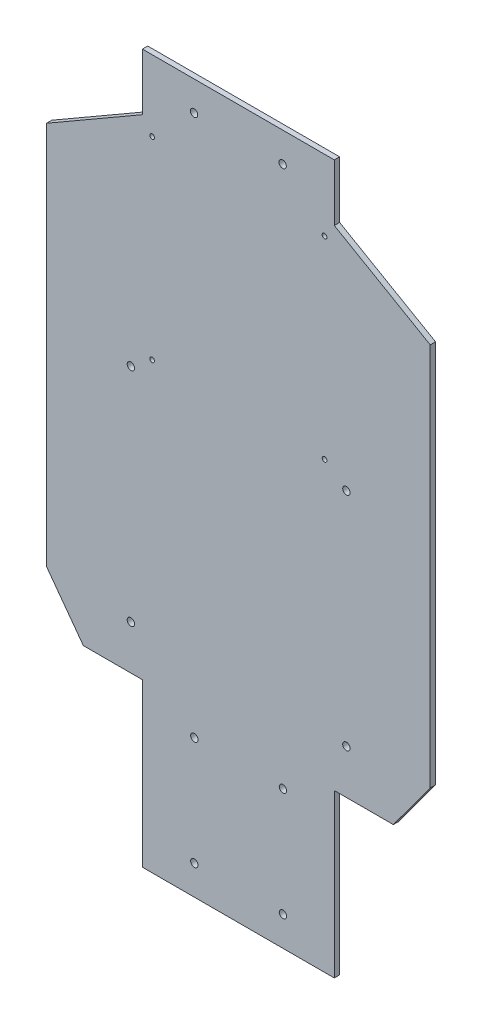
SolidWorks part; units mm, degrees
note: '?' marks a value the reader was unsure of.
ref_plane "Front Plane" through (0, 0, 0) normal (0, 0, 1) x (1, 0, 0)
ref_plane "Top Plane" through (0, 0, 0) normal (0, 1, 0) x (1, 0, 0)
ref_plane "Right Plane" through (0, 0, 0) normal (1, 0, 0) x (0, 0, -1)
sketch "Sketch1" plane through (0, 0, 0) normal (0, 0, 1) x (1, 0, 0)
  line L0 (28.575, 108.3804) -> (69.85, 84.5502)
  line L1 (-53.975, 108.3804) -> (-53.975, 132.8279)
  line L2 (-53.975, 132.8279) -> (28.575, 132.8279)
  line L3 (-53.975, -171.9721) -> (-53.975, -102.1221)
  line L4 (28.575, 132.8279) -> (28.575, 108.3804)
  line L5 (-12.7, 132.8279) -> (-12.7, -171.9721) construction
  line L6 (-95.25, -19.5721) -> (69.85, -19.5721) construction
  line L7 (-95.25, 84.5502) -> (-95.25, -135.4604) construction
  line L8 (28.575, -171.9721) -> (28.575, -102.1221)
  line L9 (69.85, 84.5502) -> (69.85, -135.4604) construction
  line L10 (-95.25, 84.5502) -> (-95.25, -80.5498)
  line L11 (69.85, 84.5502) -> (69.85, -80.5498)
  line L12 (-95.25, 84.5502) -> (-53.975, 108.3804)
  line L13 (-53.975, -102.1221) -> (-79.375, -102.1221)
  line L14 (-53.975, -171.9721) -> (28.575, -171.9721)
  line L15 (28.575, -102.1221) -> (53.975, -102.1221)
  line L16 (-95.25, -80.5498) -> (-79.375, -102.1221)
  line L17 (53.975, -102.1221) -> (69.85, -80.5498)
  line L22 (-95.25, 84.5502) -> (69.85, 84.5502) construction
  line L23 (-95.25, -103.4899) -> (69.85, -103.4899) construction
  point P0 (-12.7, -19.5721)
  dimension "D21" = 165.1
  dimension "D22" = 165.1
  dimension "D2" = 69.85
  dimension "D3" = 21.5724
  dimension "D4" = 304.8
  dimension "D5" = 69.85
  dimension "D6" = 24.4475
  dimension "D7" = 82.55
  dimension "D8" = 82.55
  dimension "D9" = 30
  dimension "D10" = 30
  dimension "D11" = 47.6603
  dimension "D12" = 47.6603
  dimension "D13" = 24.4475
  dimension "D14" = 21.5724
  dimension "D15" = 25.4
  dimension "D16" = 25.4
  dimension "D17" = 15.875
  dimension "D18" = 15.875
  dimension "D19" = 126.349
  dimension "D20" = 126.349
extrude "Boss-Extrude1" add sketch "Sketch1" along normal blind 2.286 contours L14 L8 L15 L17 L11 L0 L4 L2 L1 L12 L10 L16 L13 L3
convert to sheet metal "Convert-Solid1" [suppressed] bend radius? 10 thickness? 10
sketch "Sketch17" [suppressed] plane through (0, -151.5427, 0) normal (0, -1, 0) x (1, 0, 0)
sketch "Sketch18" plane through (0, 0, 2.286) normal (0, 0, 1) x (1, 0, 0)
  line L0 (-53.975, -171.9721) -> (28.575, -171.9721) construction
  line L1 (-53.975, -171.9721) -> (-53.975, -102.1221) construction
  line L2 (-53.975, -102.1221) -> (-79.375, -102.1221) construction
  line L3 (-53.975, 132.8279) -> (28.575, 132.8279) construction
  line L4 (-53.975, 108.3804) -> (-53.975, 132.8279) construction
  line L6 (-95.25, 84.5502) -> (-95.25, -80.5498) construction
  line L7 (28.575, -171.9721) -> (28.575, -102.1221) construction
  line L8 (-49.784, 102.3479) -> (24.384, 102.3479) construction
  line L9 (-12.7, 132.8279) -> (-12.7, 78.684) construction
  circle A0 centre (-31.623, -159.2721) radius 1.5875
  circle A1 centre (6.477, -159.2721) radius 1.5875
  circle A2 centre (-31.75, 120.1279) radius 1.5875
  circle A3 centre (6.35, 120.1279) radius 1.5875
  circle A4 centre (-58.928, -83.0721) radius 1.5875
  circle A5 centre (33.782, -83.0721) radius 1.5875
  circle A6 centre (-58.928, 12.1779) radius 1.5875
  circle A7 centre (33.782, 12.1779) radius 1.5875
  circle A8 centre (-31.623, -112.5361) radius 1.5875
  circle A9 centre (6.477, -112.5361) radius 1.5875
  circle A10 centre (-49.784, 102.3479) radius 1.016
  circle A11 centre (24.384, 102.3479) radius 1.016
  circle A12 centre (-49.784, 19.1629) radius 1.016
  circle A13 centre (24.384, 19.1629) radius 1.016
  point P44 (-12.7, 102.3479)
  dimension "D1" = 3.175
  dimension "D2" = 3.175
  dimension "D6" = 3.175
  dimension "D7" = 3.175
  dimension "D11" = 3.175
  dimension "D13" = 3.175
  dimension "D16" = 3.175
  dimension "D17" = 3.175
  dimension "D21" = 3.175
  dimension "D22" = 3.175
  dimension "D27" = 2.032
  dimension "D28" = 2.032
  dimension "D29" = 2.032
  dimension "D30" = 2.032
  dimension "D3" = 12.7
  dimension "D4" = 22.352
  dimension "D5" = 38.1
  dimension "D8" = 12.7
  dimension "D9" = 22.225
  dimension "D10" = 38.1
  dimension "D12" = 88.9
  dimension "D14" = 36.322
  dimension "D15" = 92.71
  dimension "D18" = 95.25
  dimension "D19" = 36.322
  dimension "D20" = 92.71
  dimension "D23" = 10.414
  dimension "D24" = 22.352
  dimension "D25" = 38.1
  dimension "D26" = 30.48
  dimension "D31" = 74.168
  dimension "D33" = 83.185
  dimension "D35" = 304.8
  dimension "D36" = 74.168
  dimension "D37" = 22.098
  dimension "D38" = 69.85
extrude "Cut-Extrude1" cut sketch "Sketch18" against normal up to surface (2.286 mm away) normal cut yes up to face at (-12.7, -18.7154, 0)
sketch "Bend-Lines1" [suppressed] plane through (0, 0, 0) normal (0, 1, 0) x (1, 0, 0)
sketch "Bounding-Box1" [suppressed] plane through (0, 0, 0) normal (0, 1, 0) x (1, 0, 0)
sheet metal parameters "Sheet-Metal3" thickness 10 parameters "D1"=10
flat pattern "Flat-Pattern3" [suppressed]
sketch "Bend-Lines2" plane through (0, 0, 0) normal (0, 1, 0) x (1, 0, 0)
sketch3d "Bounding-Box2" [suppressed]
  line L0 (95.25, 151.5427, 0) -> (95.25, -151.5427, 0) construction
  line L1 (-95.25, 151.5427, 0) -> (-95.25, -151.5427, 0) construction
  line L2 (95.25, 151.5427, 0) -> (-95.25, 151.5427, 0) construction
  line L3 (95.25, -151.5427, 0) -> (-95.25, -151.5427, 0) construction
